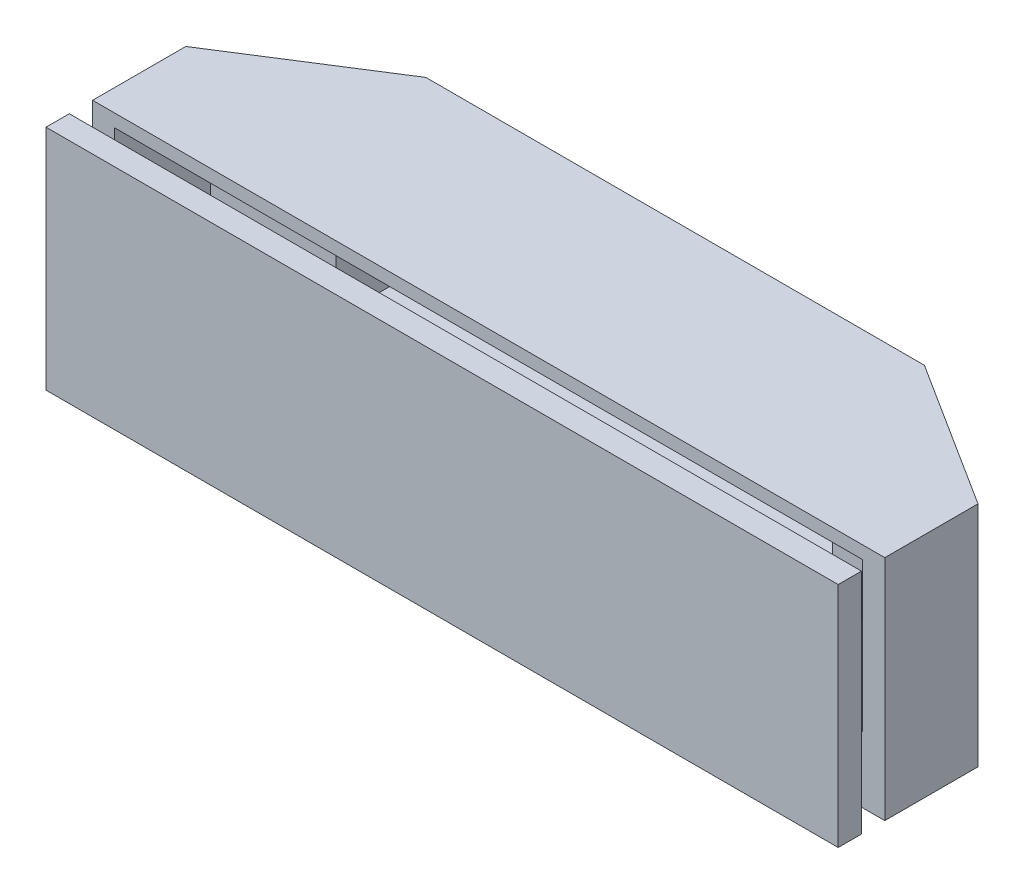
SolidWorks part; units mm, degrees
ref_plane "Front Plane" through (0, 0, 0) normal (0, 0, 1) x (1, 0, 0)
ref_plane "Top Plane" through (0, 0, 0) normal (0, 1, 0) x (1, 0, 0)
ref_plane "Right Plane" through (0, 0, 0) normal (1, 0, 0) x (0, 0, -1)
sketch "Sketch1" plane through (0, 0, 0) normal (0, 0, 1) x (1, 0, 0)
  line L1 (-21.3, 6.4) -> (21.3, 6.4)
  line L2 (-21.3, 6.4) -> (-21.3, -6.4)
  line L3 (-21.3, -6.4) -> (21.3, -6.4)
  line L4 (21.3, 6.4) -> (21.3, -6.4)
  line L5 (-21.3, 6.4) -> (21.3, -6.4) construction
  line L6 (-21.3, -6.4) -> (21.3, 6.4) construction
  point P0 (0, 0)
  dimension "D1" = 42.6
  dimension "D2" = 12.8
sketch "Sketch2" plane through (0, 0, 0) normal (0, 1, 0) x (1, 0, 0)
  line L5 (-34, 0.0554) -> (-21.4, 8.0554)
  line L6 (-21.4, 8.0554) -> (21.4, 8.0554)
  line L8 (0, -1.5931) -> (0, 13.1633) construction
  line L9 (21.4, 8.0554) -> (34, 0.0554)
  line L10 (34, 0.0554) -> (34, -7.9446)
  line L11 (34, -7.9446) -> (-34, -7.9446)
  line L12 (-34, -7.9446) -> (-34, 0.0554)
  point P2 (-34, -5.06)
  point P8 (-34, -6.2313)
  point P9 (-34, 0)
  dimension "D1" = 16
  dimension "D2" = 68
  dimension "D3" = 42.8
  dimension "D4" = 8
extrude "Boss-Extrude1" add sketch "Sketch2" along normal blind 7.5 and the other way blind 12.05
extrude "Cut-Extrude1" cut sketch "Sketch1" against normal blind 7.2
extrude "Cut-Extrude2" cut sketch "Sketch1<2>" along normal through all
sketch "Sketch1<2>" plane through (0, 0, 0) normal (0, 0, 1) x (1, 0, 0) same geometry as "Sketch1"
sketch "Sketch3" plane through (0, 0, 7.9446) normal (0, 0, 1) x (1, 0, 0)
  line L1 (-32.1, 6.4) -> (32.1, 6.4)
  line L2 (-32.1, 6.4) -> (-32.1, -6.4)
  line L3 (-32.1, -6.4) -> (32.1, -6.4)
  line L4 (32.1, 6.4) -> (32.1, -6.4)
  line L5 (-32.1, 6.4) -> (32.1, -6.4) construction
  line L6 (-32.1, -6.4) -> (32.1, 6.4) construction
  point P0 (0, 0)
  dimension "D1" = 12.8
  dimension "D2" = 64.2
extrude "Cut-Extrude3" cut sketch "Sketch3" against normal blind 8.2
sketch "Sketch4" plane through (0, 0, 7.9446) normal (0, 0, 1) x (1, 0, 0)
  line L4 (34, -12.05) -> (34, 7.5)
  line L5 (34, 7.5) -> (-34, 7.5)
  line L6 (-34, 7.5) -> (-34, -12.05)
  line L7 (-34, -12.05) -> (34, -12.05)
  line L8 (34, -12.05) -> (34, 7.5)
  line L9 (34, 7.5) -> (-34, 7.5)
  line L10 (-34, 7.5) -> (-34, -12.05)
  line L11 (-34, -12.05) -> (34, -12.05)
  dimension "D1" = 0
extrude "Boss-Extrude2" add sketch "Sketch4" along normal blind 2 from offset 2 separate body
